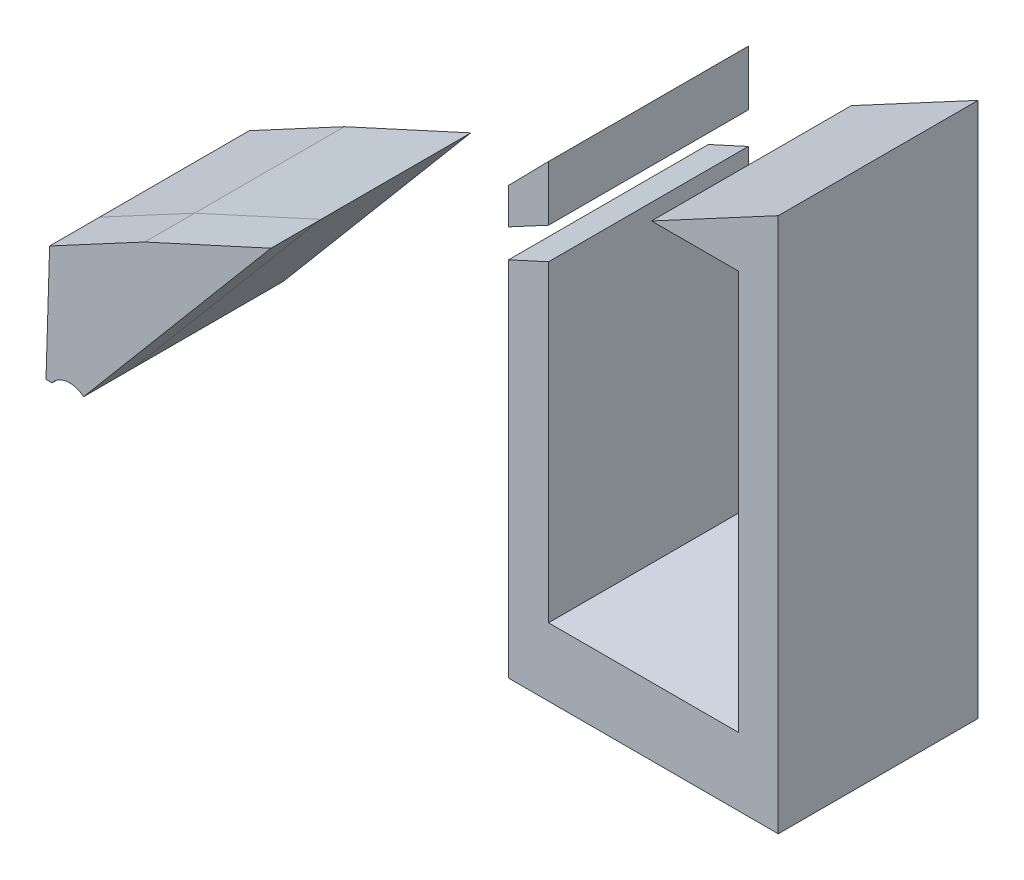
SolidWorks part; units mm, degrees
note: The reader was unsure of these and kept them because the rebuilt part matched: shared geometry of "Sketch1<3>", "Sketch1<4>".
ref_plane "Front Plane" through (0, 0, 0) normal (0, 0, 1) x (1, 0, 0)
ref_plane "Top Plane" through (0, 0, 0) normal (0, 1, 0) x (1, 0, 0)
ref_plane "Right Plane" through (0, 0, 0) normal (1, 0, 0) x (0, 0, -1)
sketch "Sketch1" plane through (0, 0, 0) normal (0, 0, 1) x (1, 0, 0)
  line L5 (-90.5, 220) -> (-90.5, 180)
  line L6 (-90.5, 180) -> (-109.5, 180)
  line L10 (-90.5, 220) -> (-157.9062, 189.1514) construction
  line L11 (-159.506, 185.9493) -> (-159.4519, 187.6985) construction
  line L12 (-159.506, 185.9493) -> (-158.9167, 185.9311) construction
  line L13 (-159.5833, 183.4505) -> (-158.9939, 183.4323) construction
  line L14 (-159.8151, 175.9541) -> (-159.5833, 183.4505) construction
  line L15 (-159.8151, 175.9541) -> (-159.2258, 175.9359) construction
  line L16 (-159.8924, 173.4553) -> (-159.3031, 173.4371) construction
  line L17 (-159.9465, 171.7061) -> (-159.8924, 173.4553) construction
  line L18 (-109.5, 220) -> (-158.4936, 170.1605) construction
  line L19 (-90.5, 220) -> (-157.9062, 189.1514)
  line L20 (-159.506, 185.9493) -> (-159.4519, 187.6985)
  line L21 (-159.506, 185.9493) -> (-158.9167, 185.9311)
  line L22 (-159.5833, 183.4505) -> (-158.9939, 183.4323)
  line L23 (-159.8151, 175.9541) -> (-159.5833, 183.4505)
  line L24 (-159.8151, 175.9541) -> (-159.2258, 175.9359)
  line L25 (-159.8924, 173.4553) -> (-159.3031, 173.4371)
  line L26 (-159.9465, 171.7061) -> (-159.8924, 173.4553)
  line L27 (-109.5, 220) -> (-158.4936, 170.1605)
  line L29 (-109.5, 220) -> (-90.5, 220)
  line L30 (-109.5, 180) -> (-109.5, 220)
  line L31 (-90.5, 200) -> (-109.5, 200) construction
  line L32 (-109.5, 180) -> (-90.5, 180)
  line L33 (-109.5, 180) -> (-109.5, 174.7)
  line L34 (-108, 173.2) -> (-106.25, 173.2)
  line L35 (-106.25, 173.2) -> (-106.25, 173.7896)
  line L36 (-103.75, 173.2) -> (-103.75, 173.7896)
  line L37 (-103.75, 173.2) -> (-96.25, 173.2)
  line L38 (-96.25, 173.2) -> (-96.25, 173.7896)
  line L39 (-93.75, 173.2) -> (-93.75, 173.7896)
  line L40 (-93.75, 173.2) -> (-92, 173.2)
  line L41 (-90.5, 180) -> (-90.5, 174.7)
  line L42 (-86.5, 220) -> (-86.5, 180)
  line L43 (-86.5, 220) -> (-86.5, 226.8)
  line L44 (-90.5, 180) -> (-86.5, 180)
  line L45 (-113.5, 180) -> (-113.5, 220)
  line L46 (-109.5, 180) -> (-113.5, 180)
  line L47 (-109.5, 220) -> (-113.5, 220)
  line L48 (-86.5, 220) -> (-90.5, 220)
  line L49 (-86.5, 180) -> (-90.5, 180)
  line L50 (-109.5, 180) -> (-113.5, 180)
  line L51 (-109.5, 220) -> (-113.5, 220)
  line L52 (-86.5, 226.8) -> (-159.4519, 187.6985)
  line L53 (-113.5, 220) -> (-113.5, 226.8)
  line L54 (-113.5, 226.8) -> (-159.9465, 171.7061)
  line L55 (-86.5, 180) -> (-86.5, 173.2)
  line L56 (-86.5, 173.2) -> (-92, 173.2)
  line L57 (-113.5, 180) -> (-113.5, 173.2)
  line L58 (-113.5, 173.2) -> (-108, 173.2)
  arc A0 (-157.9062, 189.1514) -> (-159.4519, 187.6985) centre (-157.9526, 187.6521) ccw construction
  arc A1 (-158.9939, 183.4323) -> (-158.9167, 185.9311) centre (-157.1458, 184.6257) ccw construction
  arc A2 (-159.3031, 173.4371) -> (-159.2258, 175.9359) centre (-157.4549, 174.6305) ccw construction
  arc A3 (-159.9465, 171.7061) -> (-158.4936, 170.1605) centre (-158.4472, 171.6598) ccw construction
  arc A4 (-157.9062, 189.1514) -> (-159.4519, 187.6985) centre (-157.9526, 187.6521) ccw
  arc A5 (-158.9939, 183.4323) -> (-158.9167, 185.9311) centre (-157.1458, 184.6257) ccw
  arc A6 (-159.3031, 173.4371) -> (-159.2258, 175.9359) centre (-157.4549, 174.6305) ccw
  arc A7 (-159.9465, 171.7061) -> (-158.4936, 170.1605) centre (-158.4472, 171.6598) ccw
  arc A8 (-108, 173.2) -> (-109.5, 174.7) centre (-108, 174.7) cw
  arc A9 (-106.25, 173.7896) -> (-103.75, 173.7896) centre (-105, 175.6) cw
  arc A10 (-96.25, 173.7896) -> (-93.75, 173.7896) centre (-95, 175.6) cw
  arc A11 (-90.5, 174.7) -> (-92, 173.2) centre (-92, 174.7) cw
  point P0 (0, 0)
  dimension "D1" = 40
  dimension "D2" = 4
  dimension "D3" = 4
extrude "Boss-Extrude2" add sketch "Sketch1" along normal blind 15 contours L26 A7 L27 L29 L19 A4 L20 L21 A5 L22 L23 L24 A6 L25 | A11 L41 L6 L33 A8 L34 L35 A9 L36 L37 L38 A10 L39 L40
extrude "Boss-Extrude3" add sketch "Sketch1<3>" along normal blind 20 separate body
sketch "Sketch1<3>" plane through (0, 0, 0) normal (0, 0, 1) x (1, 0, 0) same geometry as "Sketch1"
extrude "Boss-Extrude4" add sketch "Sketch1<4>" along normal blind 20 contours A4 L19 L48 L43 L52 | A7 L54 L53 L47 L27 | L41 A11 L56 L55 L44 | L58 A8 L33 L46 L57
sketch "Sketch1<4>" plane through (0, 0, 0) normal (0, 0, 1) x (1, 0, 0) same geometry as "Sketch1"
sketch "Sketch2" plane through (0, 0, 15) normal (0, 0, 1) x (1, 0, 0)
  line L0 (-162.3151, 175.9541) -> (-159.8151, 175.9541)
  line L1 (-159.5833, 183.4505) -> (-159.506, 185.9493)
  line L2 (-93.75, 173.2) -> (-96.25, 173.2)
  line L3 (-103.75, 173.2) -> (-106.25, 173.2)
  line L10 (-156.0523, 176.3254) -> (-137.2822, 198.59)
  line L11 (-156.0523, 176.3254) -> (-137.2822, 198.59)
  line L12 (-137.2822, 198.59) -> (-149.9349, 192.7995)
  line L13 (-137.2822, 198.59) -> (-149.9349, 192.7995)
  line L14 (-159.4519, 187.6985) -> (-159.506, 185.9493)
  line L15 (-159.506, 185.9493) -> (-158.9167, 185.9311)
  line L16 (-158.9939, 183.4323) -> (-159.5833, 183.4505)
  line L17 (-159.5833, 183.4505) -> (-159.8151, 175.9541)
  line L18 (-159.8151, 175.9541) -> (-159.2258, 175.9359)
  line L19 (-149.9349, 192.7995) -> (-159.4519, 187.6985)
  line L24 (-159.4519, 187.6985) -> (-159.506, 185.9493)
  line L25 (-159.506, 185.9493) -> (-158.9167, 185.9311)
  line L26 (-158.9939, 183.4323) -> (-159.5833, 183.4505)
  line L27 (-159.5833, 183.4505) -> (-159.8151, 175.9541)
  line L28 (-159.8151, 175.9541) -> (-159.2258, 175.9359)
  line L32 (-90.5, 174.7) -> (-90.5, 180)
  line L33 (-90.5, 180) -> (-109.5, 180)
  line L34 (-109.5, 180) -> (-109.5, 174.7)
  line L35 (-108, 173.2) -> (-106.25, 173.2)
  line L36 (-106.25, 173.2) -> (-106.25, 173.7896)
  line L37 (-103.75, 173.7896) -> (-103.75, 173.2)
  line L38 (-103.75, 173.2) -> (-96.25, 173.2)
  line L39 (-96.25, 173.2) -> (-96.25, 173.7896)
  line L40 (-93.75, 173.7896) -> (-93.75, 173.2)
  line L41 (-93.75, 173.2) -> (-92, 173.2)
  line L42 (-90.5, 174.7) -> (-90.5, 180)
  line L43 (-90.5, 180) -> (-109.5, 180)
  line L44 (-109.5, 180) -> (-109.5, 174.7)
  line L45 (-108, 173.2) -> (-106.25, 173.2)
  line L46 (-106.25, 173.2) -> (-106.25, 173.7896)
  line L47 (-103.75, 173.7896) -> (-103.75, 173.2)
  line L48 (-103.75, 173.2) -> (-96.25, 173.2)
  line L49 (-96.25, 173.2) -> (-96.25, 173.7896)
  line L50 (-93.75, 173.7896) -> (-93.75, 173.2)
  line L51 (-93.75, 173.2) -> (-92, 173.2)
  line L52 (-149.9349, 192.7995) -> (-159.4519, 187.6985)
  arc A6 (-158.9939, 183.4323) -> (-158.9167, 185.9311) centre (-157.1458, 184.6257) ccw
  arc A7 (-156.0523, 176.3254) -> (-159.2258, 175.9359) centre (-157.4549, 174.6305) ccw
  arc A10 (-158.9939, 183.4323) -> (-158.9167, 185.9311) centre (-157.1458, 184.6257) ccw
  arc A11 (-156.0523, 176.3254) -> (-159.2258, 175.9359) centre (-157.4549, 174.6305) ccw
  arc A12 (-92, 173.2) -> (-90.5, 174.7) centre (-92, 174.7) ccw
  arc A13 (-109.5, 174.7) -> (-108, 173.2) centre (-108, 174.7) ccw
  arc A14 (-103.75, 173.7896) -> (-106.25, 173.7896) centre (-105, 175.6) ccw
  arc A15 (-93.75, 173.7896) -> (-96.25, 173.7896) centre (-95, 175.6) ccw
  arc A16 (-92, 173.2) -> (-90.5, 174.7) centre (-92, 174.7) ccw
  arc A17 (-109.5, 174.7) -> (-108, 173.2) centre (-108, 174.7) ccw
  arc A18 (-103.75, 173.7896) -> (-106.25, 173.7896) centre (-105, 175.6) ccw
  arc A19 (-93.75, 173.7896) -> (-96.25, 173.7896) centre (-95, 175.6) ccw
  dimension "D1" = 0
  dimension "D2" = 0
extrude "Boss-Extrude5" add sketch "Sketch2" along normal up to surface (5 mm away)
